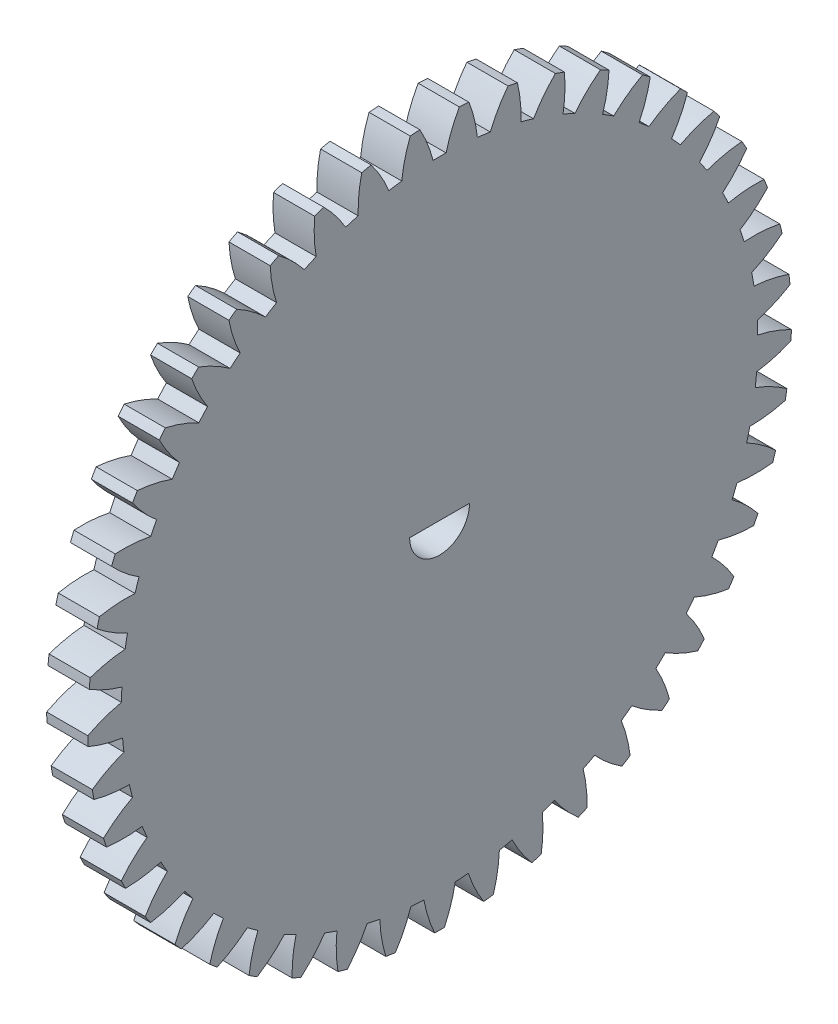
SolidWorks part; units mm, degrees
ref_plane "Plane1" through (0, 0, 0) normal (0, 0, 1) x (1, 0, 0)
ref_plane "Plane2" through (0, 0, 0) normal (0, 1, 0) x (1, 0, 0)
ref_plane "Plane3" through (0, 0, 0) normal (1, 0, 0) x (0, 0, -1)
sketch "HoldingSke" plane through (0, 0, 0) normal (0, 1, 0) x (1, 0, 0)
  line L0 (0, 0) -> (0.3536, -0.3536)
  line L1 (-15, 0) -> (100, 0) construction
  line L2 (0, 0) -> (-2.1039, 2.3779)
  line L3 (0, 0) -> (-11.863, 4.5341)
  line L4 (0, 0) -> (6.1066, 6.1066)
  line L5 (0, 0) -> (-46.8476, -17.4728)
  line L6 (0, 0) -> (-4.5593, -3.0762)
  line L7 (-2.1039, 2.3779) -> (8.6586, 51.2059)
  line L8 (-76.2, 54.61) -> (-76.1, 54.61)
  line L9 (-71.009, 38.7566) -> (-53.1078, 45.2721)
  line L10 (-76.2, 71.12) -> (104.1128, 71.12)
  line L11 (0, 0) -> (-5.5, 0)
  line L12 (-76.2, 101.6) -> (-76.133, 101.6)
  line L13 (24.9733, 27.94) -> (52.9518, 28.4284)
  line L14 (24.9733, 27.94) -> (24.9743, 27.94)
  line L15 (24.9733, 27.94) -> (100.4006, 29.5858)
  line L16 (-63.627, -2) -> (-12.827, -2)
  circle A0 centre (0, 0) radius 0.4
  circle A1 centre (0, 0) radius 37.5
  circle A2 centre (0, 0) radius 37.5
  circle A3 centre (0, 0) radius 0.4
  dimension "MHD" = 75
  dimension "Hub_dia" = 75
  dimension "Bore" = 0.8
  dimension "MBD" = 0.8
  dimension "Num_teeth" = 45
  dimension "Pitch" = 0.5
  dimension "Overall_len" = 50
  dimension "Show_teeth" = 45
  dimension "Thickness" = 5.5
  dimension "OAL" = 50.0001
  dimension "T_dim" = 0.1
  dimension "Ap" = 20
  dimension "H" = 19.05
  dimension "Pitch_radius" = 180.3128
  dimension "Width" = 5.5
  dimension "Backlash" = 0.067
  dimension "Addendum_fac" = 1
  dimension "Dedendum_fac" = 1.25
  dimension "Clearance_fac" = 0.25
  dimension "Dedendum_add" = 0.001
  dimension "Module" = 2
sketch "BasProSke" plane through (0, 0, 0) normal (0, 1, 0) x (1, 0, 0)
  line L0 (-10, 0) -> (60, 0) construction
  line L1 (0, 0) -> (0, 47)
  line L2 (0, 0) -> (5.5, 0)
  line L3 (5.5, 0) -> (5.5, 47)
  line L4 (5.5, 47) -> (0, 47)
  dimension "Thickness" = 5.5
  dimension "Diameter" = 94
revolve "Base-Revolve" add sketch "BasProSke" angle 360 about L0
sketch "TooCutSke" plane through (0, 0, 0) normal (1, 0, 0) x (0, 0, -1)
  line L1 (0, 0) -> (0, 107) construction
  line L2 (0, 0) -> (-1.6877, 44.9683) construction
  line L3 (0, 0) -> (-6.2748, 89.7339) construction
  line L4 (-1.6877, 44.9683) -> (-3.1374, 44.867) construction
  arc A0 (0.8706, 42.4901) -> (-0.8706, 42.4901) centre (0, 0) ccw
  arc A1 (2.6509, 46.9506) -> (-2.6509, 46.9506) centre (0, 0) ccw
  circle A2 centre (0, 0) radius 45 construction
  circle A3 centre (0, 0) radius 42.2862 construction
  arc A4 (-0.8706, 42.4901) -> (-2.6509, 46.9506) centre (-18.3289, 38.1074) ccw
  arc A5 (2.6509, 46.9506) -> (0.8706, 42.4901) centre (18.3289, 38.1074) ccw
  dimension "Root_dia" = 84.998
  dimension "Overcut_dia" = 94.0508
  dimension "Pitch_dia" = 90
  dimension "Base_dia" = 84.5723
  dimension "Flank_rad" = 18
  dimension "Half_ang" = 4
  dimension "Half_CT" = 1.4532
extrude "ToothCut" cut sketch "TooCutSke" along normal through all
fillet "Breaks" [suppressed] radius 0.04 tangent propagation no
fillet "RootFillets" [suppressed] radius 0.501
pattern_circular "TeethCuts" count 45 every 8 about axis through (-10, 0, 0) along (1, 0, 0) of "ToothCut", "RootFillets", "Breaks"
sketch "HubNeaOneSke" plane through (0, 0, 0) normal (-1, 0, 0) x (0, 0, 1)
  circle A0 centre (0, 0) radius 37.5
  dimension "Diameter" = 75
extrude "HubNearOne" [suppressed] add sketch "HubNeaOneSke" along normal blind 44.5001
sketch "HubNeaBotSke" plane through (0, 0, 0) normal (-1, 0, 0) x (0, 0, 1)
  circle A0 centre (0, 0) radius 37.5
  dimension "Diameter" = 75
extrude "HubNearBoth" [suppressed] add sketch "HubNeaBotSke" along normal blind 22.25
ref_plane "FarPln" through (5.5, 0, 0) normal (1, 0, 0) x (0, 0, -1)
sketch "HubFarSke" plane through (5.5, 0, 0) normal (1, 0, 0) x (0, 0, -1)
  circle A0 centre (0, 0) radius 37.5
  dimension "Diameter" = 75
extrude "HubFar" [suppressed] add sketch "HubFarSke" along normal blind 22.25
sketch "BorSke" plane through (0, 0, 0) normal (1, 0, 0) x (0, 0, -1)
  circle A0 centre (0, 0) radius 0.4
  dimension "Diameter" = 0.8
extrude "Bore" cut sketch "BorSke" along normal mid plane 100.0001
sketch "KeySke" plane through (0, 0, 0) normal (1, 0, 0) x (0, 0, -1)
  line L0 (-0.05, 0) -> (-0.05, 0.5)
  line L1 (-0.05, 0.5) -> (0.05, 0.5)
  line L2 (0.05, 0.5) -> (0.05, 0)
  line L3 (0, 0) -> (0, 34) construction
  line L4 (-0.05, 0) -> (0.05, 0)
  dimension "Offset" = 0.5
  dimension "Width" = 0.1
extrude "Keyway" [suppressed] cut sketch "KeySke" along normal mid plane 100.0001
pattern_circular "Keyway2" [suppressed] count 2 every 90 about axis through (-10, 0, 0) along (1, 0, 0)
sketch "Croquis1" plane through (5.5, 0, 0) normal (1, 0, 0) x (0, 0, -1)
  line L0 (-4, 0.4) -> (4, 0.4)
  arc A0 (-4, 0.4) -> (4, 0.4) centre (0, 0.4) ccw
  circle A1 centre (0, 0) radius 0.4 construction
  dimension "D1" = 8
extrude "Cortar-Extruir1" cut sketch "Croquis1" against normal blind 6
equation "' \"Module@HoldingSke\" = 6.35"
equation "' \"Num_teeth@HoldingSke\" = 12"
equation "' \"Ap@HoldingSke\" =  20"
equation "' \"Ap@HoldingSke\" = 20"
equation "' \"Width@HoldingSke\" = 0.5 * 25.4"
equation "' \"Hub_dia@HoldingSke\"= 1 * 25.4"
equation "' \"Hub_dia@HoldingSke\" = 1 * 25.4"
equation "' \"Overall_len@HoldingSke\" = 1.0 * 25.4"
equation "' \"Bore@HoldingSke\" = 0.75 * 25.4"
equation "' \"T_dim@HoldingSke\" = 0.1 * 25.4"
equation "' \"Width@KeySke\" = 0.25 * 25.4"
equation "' \"Show_teeth@HoldingSke\" = 13"
equation "' \"Backlash@HoldingSke\" = 0.009 * 25.4"
equation "' \"Addendum_fac@HoldingSke\" = 1.0"
equation "' \"Dedendum_fac@HoldingSke\" = 1.25"
equation "' \"Dedendum_add@HoldingSke\" = 0.00005 * 25.4"
equation "' \"Clearance_fac@HoldingSke\" = 0.25"
equation "\"Pitch@HoldingSke\" = 1 / \"Module@HoldingSke\""
equation "\"Overcut_dia@TooCutSke\" = (\"Num_teeth@HoldingSke\" + 2 * \"Addendum_fac@HoldingSke\") / \"Pitch@HoldingSke\" + 0.002 * 25.4"
equation "\"Pitch_dia@TooCutSke\" = \"Num_teeth@HoldingSke\" / \"Pitch@HoldingSke\""
equation "\"Base_dia@TooCutSke\" = \"Num_teeth@HoldingSke\" / \"Pitch@HoldingSke\" * cos((\"Ap@HoldingSke\"  * 3.14159265 / 180))"
equation "\"Root_dia@TooCutSke\" = (\"Num_teeth@HoldingSke\" + 2) / \"Pitch@HoldingSke\" - 2 * (\"Addendum_fac@HoldingSke\" + \"Dedendum_fac@HoldingSke\") / \"Pitch@HoldingSke\" - \"Dedendum_add@HoldingSke\" * 2"
equation "\"Half_ang@TooCutSke\" = 180 / \"Num_teeth@HoldingSke\""
equation "\"Half_CT@TooCutSke\" = \"Num_teeth@HoldingSke\" / \"Pitch@HoldingSke\" * sin((3.14159265 / 2 / \"Num_teeth@HoldingSke\")) / 2 - 7 * \"Backlash@HoldingSke\" / 4"
equation "\"Flank_rad@TooCutSke\" = \"Num_teeth@HoldingSke\" / \"Pitch@HoldingSke\" / 5"
equation "\"Radius@RootFillets\" = \"Clearance_fac@HoldingSke\" / \"Pitch@HoldingSke\" + \"Dedendum_add@HoldingSke\""
equation "\"Break_rad@Breaks\" = 0.02 / \"Pitch@HoldingSke\""
equation "\"Thickness@HoldingSke\" = \"Width@HoldingSke\""
equation "\"OAL@HoldingSke\" = \"Thickness@HoldingSke\""
equation "\"MHD@HoldingSke\" = (\"Num_teeth@HoldingSke\" + 2) / \"Pitch@HoldingSke\" - 2 * (\"Addendum_fac@HoldingSke\" + \"Dedendum_fac@HoldingSke\")  / \"Pitch@HoldingSke\" - \"Dedendum_add@HoldingSke\" * 2"
equation "\"MBD@HoldingSke\" = (\"Num_teeth@HoldingSke\" + 2) / \"Pitch@HoldingSke\" - 2 * (\"Addendum_fac@HoldingSke\" + \"Dedendum_fac@HoldingSke\")  / \"Pitch@HoldingSke\" - \"Dedendum_add@HoldingSke\" * 2 - 0.002 * 25.4"
equation "\"MHD@HoldingSke\" = ((sgn( \"MHD@HoldingSke\" - \"Hub_dia@HoldingSke\" )-1)*( \"MHD@HoldingSke\" - \"Hub_dia@HoldingSke\" ))/-2+ \"Hub_dia@HoldingSke\""
equation "\"MBD@HoldingSke\" = ((sgn( \"MBD@HoldingSke\" - \"Bore@HoldingSke\" )-1)*( \"MBD@HoldingSke\" - \"Bore@HoldingSke\" ))/-2+ \"Bore@HoldingSke\""
equation "\"OAL@HoldingSke\" = ((sgn( \"OAL@HoldingSke\" - \"Overall_len@HoldingSke\" )+1)*( \"OAL@HoldingSke\" - \"Overall_len@HoldingSke\" ))/2 + \"Overall_len@HoldingSke\" + 0.000002 * 25.4"
equation "\"Num_teeth@TeethCuts\" = int( \"Show_teeth@HoldingSke\" ) + 1"
equation "\"Num_teeth@TeethCuts\" = ((sgn( \"Num_teeth@TeethCuts\" - \"Num_teeth@HoldingSke\" )-1)*( \"Num_teeth@TeethCuts\" - \"Num_teeth@HoldingSke\" ))/-2+ \"Num_teeth@HoldingSke\""
equation "\"Num_teeth@TeethCuts\" = ((sgn( \"Num_teeth@TeethCuts\" - 2.0)+1)*( \"Num_teeth@TeethCuts\" - 2.0))/2 +2.0"
equation "\"Angle@TeethCuts\" = 360.0 / \"Num_teeth@HoldingSke\""
equation "\"Diameter@BasProSke\" = (\"Num_teeth@HoldingSke\" + 2 * \"Addendum_fac@HoldingSke\") / \"Pitch@HoldingSke\""
equation "\"Thickness@BasProSke\"  = \"Thickness@HoldingSke\""
equation "' \"Fillet_rad@BasProSke\" =  \"Thickness@HoldingSke\" * 0.05"
equation "' \"Fillet_rad@BasProSke\" = \"Thickness@HoldingSke\" * 0.05"
equation "\"MHD@HoldingSke\" = ((sgn( \"MHD@HoldingSke\" - \"Root_dia@TooCutSke\" )-1)*( \"MHD@HoldingSke\" - \"Root_dia@TooCutSke\" ))/-2+ \"Root_dia@TooCutSke\""
equation "\"Diameter@HubNeaOneSke\" = \"MHD@HoldingSke\""
equation "\"Length@HubNearOne\" = \"OAL@HoldingSke\" - \"Thickness@BasProSke\""
equation "\"Diameter@HubNeaBotSke\" = \"MHD@HoldingSke\""
equation "\"Length@HubNearBoth\" = ( \"OAL@HoldingSke\" - \"Thickness@BasProSke\" ) / 2.0"
equation "\"Thickness@FarPln\" = \"Thickness@BasProSke\""
equation "\"Diameter@HubFarSke\" = \"MHD@HoldingSke\""
equation "\"Length@HubFar\" = ( \"OAL@HoldingSke\" - \"Thickness@BasProSke\" ) / 2.0"
equation "\"Diameter@BorSke\" = \"MBD@HoldingSke\""
equation "\"D1@Bore\" = \"OAL@HoldingSke\" * 2.0"
equation "\"D1@Keyway\" = \"OAL@HoldingSke\" * 2.0"
equation "\"Offset@KeySke\" = \"T_dim@HoldingSke\" + \"MBD@HoldingSke\" / 2.0"
